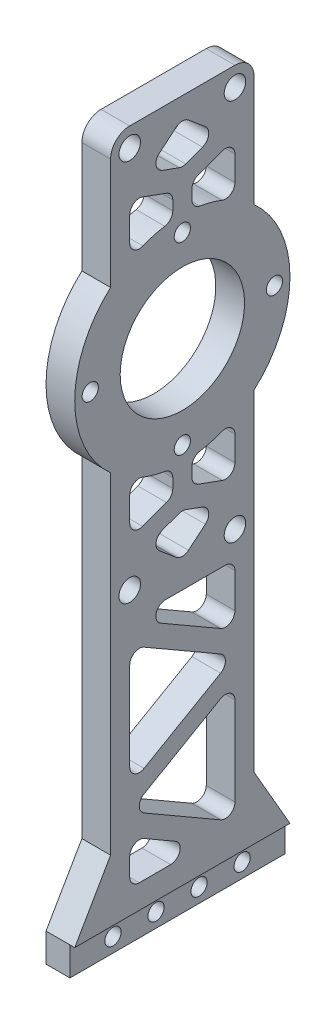
SolidWorks part; units mm, degrees
material "Сплав 2024"
ref_plane "Спереди" through (0, 0, 0) normal (0, 0, 1) x (1, 0, 0)
ref_plane "Сверху" through (0, 0, 0) normal (0, 1, 0) x (1, 0, 0)
ref_plane "Справа" through (0, 0, 0) normal (1, 0, 0) x (0, 0, -1)
sketch "Эскиз1" plane through (0, 0, 0) normal (0, 1, 0) x (1, 0, 0)
  line L1 (0, 0) -> (6, 0)
  line L2 (0, 0) -> (0, -30)
  line L3 (0, -30) -> (6, -30)
  line L4 (6, 0) -> (6, -30)
  dimension "D1" = 6
  dimension "D2" = 30
extrude "Бобышка-Вытянуть1" add sketch "Эскиз1" along normal blind 177
sketch "Эскиз2" plane through (0, 0, 0) normal (-1, 0, 0) x (0, 0, 1)
  line L0 (30, 105) -> (0, 105) construction
  line L3 (15, 177) -> (15, 0) construction
  line L4 (0, 177) -> (30, 177) construction
  line L5 (0, 0) -> (30, 0) construction
  line L6 (30, 0) -> (0, 0) construction
  circle A0 centre (15, 105) radius 22.5
  dimension "D1" = 45
  dimension "D2" = 105
extrude "Бобышка-Вытянуть2" add sketch "Эскиз2" against normal up to surface (6 mm away) up to face at (6, 88.5, 15)
sketch "Эскиз3" plane through (0, 0, 0) normal (-1, 0, 0) x (0, 0, 1)
  circle A0 centre (15, 105) radius 13
  dimension "D1" = 26
extrude "Вырез-Вытянуть1" cut sketch "Эскиз3" against normal through all
sketch "Эскиз4" plane through (6, 0, 0) normal (-1, 0, 0) x (0, 0, 1)
  line L0 (-7.5, 105) -> (37.5, 105) construction
  line L2 (15, 127.5) -> (15, 82.5) construction
  line L3 (30, 105) -> (0, 105) construction
  circle A0 centre (15, 105) radius 19.25 construction
  circle A1 centre (15, 105) radius 22.5 construction
  dimension "D1" = 38.5
  dimension "D2" = 90
hole_wizard "Отверстие с зазором M32" positions "Эскиз6" profile "Эскиз5" hole size "M3" standard "Ansi Metric" end condition up to next
sketch "Эскиз6" plane through (6, -25.0247, 7.2629) normal (-1, 0, 0) x (0, 0, 1)
  line L0 (-14.7629, 130.0247) -> (30.2371, 130.0247) construction
  line L1 (7.7371, 152.5247) -> (7.7371, 107.5247) construction
  circle A0 centre (7.7371, 130.0247) radius 19.25 construction
  point P0 (-11.5129, 130.0247)
  point P6 (7.7371, 110.7747)
  point P10 (26.9871, 130.0247)
  point P12 (7.7371, 149.2747)
sketch "Эскиз5" plane through (6, 105, -4.25) normal (0, 1, 0) x (0, 0, -1)
  line L0 (0, 0) -> (0, 6)
  line L1 (0, 6) -> (1.7, 6)
  line L2 (1.7, 6) -> (1.7, 0)
  line L5 (1.7, 0) -> (0, 0)
  line L11 (0, -6.35) -> (0, 107.95) construction
  dimension "Диаметр сквозного отверстия" = 3.4
  dimension "Глубина сквозного отверстия" = 6
sketch "Эскиз8" plane through (6, 0, 0) normal (1, 0, 0) x (0, 0, -1)
  line L0 (-15, 177) -> (-15, 0) construction
  line L1 (-30, 177) -> (0, 177) construction
  line L2 (-30, 0) -> (0, 0) construction
  line L3 (19.447, 105) -> (-49.447, 105) construction
  line L4 (0, 177) -> (0, 121.7705) construction
  line L5 (-26, 145) -> (-4, 145) construction
  line L6 (-26, 145) -> (-26, 65) construction
  line L7 (-26, 65) -> (-4, 65) construction
  line L8 (-4, 145) -> (-4, 65) construction
  line L9 (-26, 145) -> (-4, 65) construction
  line L10 (-26, 65) -> (-4, 145) construction
  line L11 (-30, 105) -> (0, 105) construction
  point P8 (-15, 105)
  point P9 (-15, 105)
  dimension "D1" = 4
  dimension "D2" = 80
hole_wizard "Отверстие с зазором M41" positions "Эскиз10" profile "Эскиз9" hole size "M4" standard "Ansi Metric" end condition through all
sketch "Эскиз10" plane through (6, 0, 0) normal (1, 0, 0) x (0, 0, -1)
  point P0 (-26, 145)
  point P3 (-4, 145)
  point P6 (-4, 65)
  point P9 (-26, 65)
sketch "Эскиз9" plane through (6, 145, 26) normal (0, 1, 0) x (0, 0, -1)
  line L0 (0, 0) -> (0, 6)
  line L1 (0, 6) -> (2.25, 6)
  line L2 (2.25, 6) -> (2.25, 0)
  line L5 (2.25, 0) -> (0, 0)
  line L11 (0, -6.35) -> (0, 107.95) construction
  dimension "Диаметр сквозного отверстия" = 4.5
  dimension "Глубина сквозного отверстия" = 6
sketch "Эскиз11" plane through (6, 0, 0) normal (1, 0, 0) x (0, 0, -1)
  line L0 (-30, 0) -> (0, 0) construction
  line L1 (-15, 177) -> (-15, 0) construction
  line L2 (-30, 177) -> (0, 177) construction
  line L3 (0, 88.2295) -> (0, 0) construction
  line L4 (-30, 88.2295) -> (-30, 0) construction
  line L5 (-37.5, 3) -> (7.5, 3) construction
  line L20 (-1.5, 0) -> (-1.5, 6) construction
  line L21 (-10.5, 0) -> (-10.5, 6) construction
  line L22 (-19.5, 0) -> (-19.5, 6) construction
  line L23 (-28.5, 0) -> (-28.5, 6) construction
  line L25 (-37.5, 0) -> (7.5, 6) construction
  line L26 (-37.5, 6) -> (7.5, 0) construction
  line L27 (-37.5, 6) -> (7.5, 6) construction
  line L28 (0, 18.9904) -> (7.5, 6)
  line L29 (-30, 18.9904) -> (0, 18.9904)
  line L30 (7.5, 6) -> (7.5, 0)
  line L31 (-37.5, 0) -> (7.5, 0)
  line L32 (-37.5, 6) -> (-37.5, 0)
  line L33 (-37.5, 6) -> (-30, 18.9904)
  point P2 (-15, 3)
  dimension "D1" = 45
  dimension "D2" = 6
  dimension "D3" = 9
  dimension "D4" = 9
  dimension "D5" = 9
  dimension "D6" = 9
  dimension "D7" = 120
extrude "Бобышка-Вытянуть3" add sketch "Эскиз11" against normal up to surface (6 mm away) up to face at (0, 145, 23.75)
hole_wizard "Отверстие с зазором M31" positions "Эскиз13" profile "Эскиз12" hole size "M3" standard "Ansi Metric" end condition through all
sketch "Эскиз13" plane through (6, 0, 0) normal (1, 0, 0) x (0, 0, -1)
  line L4 (-28.5, 0) -> (-28.5, 6) construction
  line L5 (-19.5, 0) -> (-19.5, 6) construction
  line L6 (-10.5, 0) -> (-10.5, 6) construction
  line L7 (-1.5, 0) -> (-1.5, 6) construction
  point P16 (-28.5, 3)
  point P20 (-19.5, 3)
  point P24 (-10.5, 3)
  point P28 (-1.5, 3)
sketch "Эскиз12" plane through (6, 3, 28.5) normal (0, 1, 0) x (0, 0, -1)
  line L0 (0, 0) -> (0, 6)
  line L1 (0, 6) -> (1.7, 6)
  line L2 (1.7, 6) -> (1.7, 0)
  line L5 (1.7, 0) -> (0, 0)
  line L11 (0, -6.35) -> (0, 107.95) construction
  dimension "Диаметр сквозного отверстия" = 3.4
  dimension "Глубина сквозного отверстия" = 6
sketch "Эскиз14" plane through (6, 0, 0) normal (1, 0, 0) x (0, 0, -1)
  line L5 (-37.5, 0) -> (7.5, 0)
  line L6 (-37.5, 0) -> (-37.5, 6)
  line L7 (-37.5, 6) -> (7.5, 6)
  line L8 (7.5, 0) -> (7.5, 6)
extrude "Вырез-Вытянуть2" cut sketch "Эскиз14" against normal blind 1
sketch "Эскиз15" plane through (6, 0, 0) normal (1, 0, 0) x (0, 0, -1)
  line L0 (0, 177) -> (0, 121.7705) construction
  line L1 (-30, 177) -> (0, 177)
  line L2 (-30, 177) -> (-30, 149.0245)
  line L3 (-30, 149.0245) -> (0, 149.0245)
  line L4 (0, 177) -> (0, 149.0245)
  circle A0 centre (-26, 145) radius 2.25 construction
  dimension "D1" = 4.0245
extrude "Вырез-Вытянуть3" cut sketch "Эскиз15" against normal up to surface (6 mm away) up to face at (0, 3, 26.8)
fillet "Скругление1" radius 4 2 edges at (3, 149.0245, 30) (3, 149.0245, 0)
sketch "Эскиз16" plane through (0, 0, 0) normal (-1, 0, 0) x (0, 0, 1)
  line L0 (4, 0) -> (4, 149.0245) construction
  line L1 (-7.5, 0) -> (37.5, 0) construction
  line L2 (4, 149.0245) -> (26, 149.0245) construction
  line L3 (26, 0) -> (26, 149.0245) construction
  line L4 (0, 88.2295) -> (0, 18.9904) construction
  line L5 (30, 88.2295) -> (30, 18.9904) construction
  line L6 (15, 177) -> (15, 0) construction
  line L7 (0, 145.0245) -> (30, 145.0245) construction
  line L8 (0, 145.0245) -> (0, 121.7705) construction
  line L9 (30, 145.0245) -> (30, 121.7705) construction
  line L10 (15, 145.0245) -> (4, 135.7944) construction
  line L11 (15, 145.0245) -> (26, 135.7944) construction
  line L12 (0, 135.7944) -> (30, 135.7944) construction
  line L13 (4, 135.7944) -> (4, 124.6278)
  line L14 (26, 135.7944) -> (26, 124.6278)
  line L15 (13, 132.5187) -> (13, 127.4109)
  line L16 (17, 132.5187) -> (17, 127.4109)
  line L17 (4, 135.7944) -> (13, 132.5187)
  line L18 (0, 132.5187) -> (30, 132.5187) construction
  line L19 (26, 135.7944) -> (17, 132.5187)
  line L20 (7.5382, 138.7634) -> (15, 136.0475)
  line L21 (22.4618, 138.7634) -> (15, 136.0475)
  line L22 (7.5382, 138.7634) -> (15, 145.0245)
  line L23 (15, 145.0245) -> (22.4618, 138.7634)
  line L24 (15, 105) -> (22.4618, 105) construction
  line L25 (13, 77.4813) -> (13, 82.5891)
  line L26 (17, 77.4813) -> (17, 82.5891)
  line L27 (26, 74.2056) -> (17, 77.4813)
  line L28 (26, 74.2056) -> (26, 85.3722)
  line L29 (4, 74.2056) -> (4, 85.3722)
  line L30 (4, 74.2056) -> (13, 77.4813)
  line L31 (7.5382, 71.2366) -> (15, 73.9525)
  line L32 (22.4618, 71.2366) -> (15, 73.9525)
  line L33 (15, 64.9755) -> (22.4618, 71.2366)
  line L34 (7.5382, 71.2366) -> (15, 64.9755)
  line L35 (26, 54.8812) -> (26, 29.4778)
  line L36 (26, 29.4778) -> (4, 42.1795)
  line L37 (4, 42.1795) -> (26, 54.8812)
  line L38 (4, 59.5) -> (26, 59.5)
  line L39 (26, 59.5) -> (4, 46.7983)
  line L40 (4, 46.7983) -> (4, 59.5)
  line L41 (4, 37.5607) -> (26, 24.859)
  line L42 (26, 24.859) -> (4, 12.1573)
  line L43 (4, 12.1573) -> (4, 37.5607)
  line L44 (9.9955, 11) -> (26, 20.2402)
  line L45 (26, 20.2402) -> (26, 11)
  line L46 (26, 11) -> (9.9955, 11)
  line L47 (34.6132, 11) -> (-4.6132, 11) construction
  line L48 (30, 18.9904) -> (37.5, 6) construction
  line L49 (-7.5, 6) -> (0, 18.9904) construction
  line L50 (-7.5, 6) -> (37.5, 6) construction
  circle A0 centre (15, 105) radius 22.5 construction
  arc A1 (4, 124.6278) -> (13, 127.4109) centre (15, 105) cw
  arc A2 (17, 127.4109) -> (26, 124.6278) centre (15, 105) cw
  arc A3 (17, 82.5891) -> (26, 85.3722) centre (15, 105) ccw
  arc A4 (4, 85.3722) -> (13, 82.5891) centre (15, 105) ccw
  circle A5 centre (4, 65) radius 2.25 construction
  point P12 (4, 124.6278)
  point P13 (26, 124.6278)
  point P20 (15, 145.0245)
  dimension "D3" = 4
  dimension "D16" = 5.5
  dimension "D1" = 4
  dimension "D2" = 4
  dimension "D4" = 100
  dimension "D5" = 4
  dimension "D6" = 2
  dimension "D7" = 4
  dimension "D8" = 110
  dimension "D9" = 30
  dimension "D10" = 4
  dimension "D11" = 4
  dimension "D12" = 4
  dimension "D13" = 60
  dimension "D14" = 60
  dimension "D15" = 5
extrude "Вырез-Вытянуть4" cut sketch "Эскиз16" against normal through all
fillet "Скругление3" radius 2 36 edges at (3, 127.4109, 13) (3, 124.6278, 26) (3, 124.6278, 4) (3, 127.4109, 17) (3, 132.5187, 17) (3, 135.7944, 4) (3, 132.5187, 13) (3, 135.7944, 26) (3, 136.0475, 15) (3, 138.7634, 22.4618) (3, 138.7634, 7.5382) (3, 145.0245, 15) (3, 71.2366, 7.5382) (3, 71.2366, 22.4618) (3, 85.3722, 4) (3, 77.4813, 17) (3, 82.5891, 17) (3, 74.2056, 4) (3, 64.9755, 15) (3, 73.9525, 15) (3, 82.5891, 13) (3, 85.3722, 26) (3, 77.4813, 13) (3, 74.2056, 26) (3, 11, 9.9955) (3, 11, 26) (3, 12.1573, 4) (3, 20.2402, 26) (3, 24.859, 26) (3, 29.4778, 26) (3, 37.5607, 4) (3, 54.8812, 26) (3, 42.1795, 4) (3, 46.7983, 4) (3, 59.5, 4) (3, 59.5, 26)
equation "\"D4@Эскиз11\"=\"D3@Эскиз11\""
equation "\"D5@Эскиз11\"=\"D3@Эскиз11\""
equation "\"D6@Эскиз11\"=\"D4@Эскиз11\""
equation "\"D3@Эскиз11\" = \"D1@Эскиз11\" / 5"
equation "\"D13@Эскиз16\"=\"D9@Эскиз16\"*2"
equation "\"D11@Эскиз16\"=\"D10@Эскиз16\""
equation "\"D12@Эскиз16\"=\"D10@Эскиз16\""
